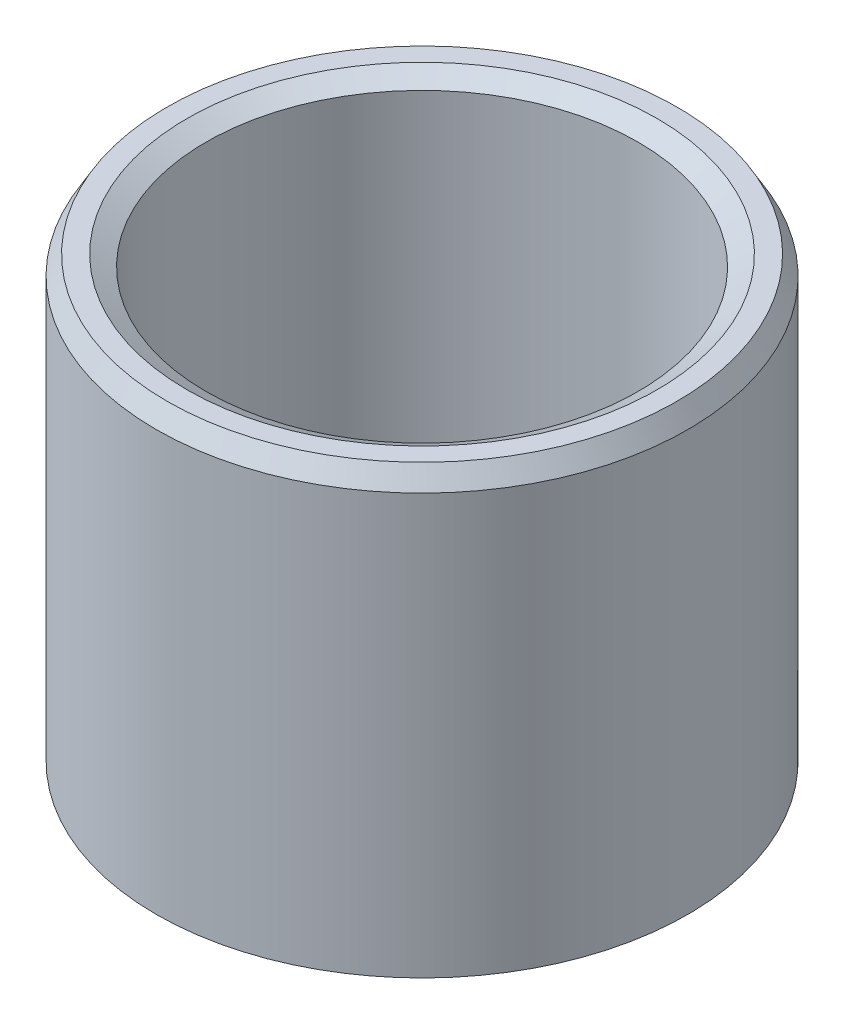
SolidWorks part; units mm, degrees
ref_plane "Front Plane" through (0, 0, 0) normal (0, 0, 1) x (1, 0, 0)
ref_plane "Top Plane" through (0, 0, 0) normal (0, 1, 0) x (1, 0, 0)
ref_plane "Right Plane" through (0, 0, 0) normal (1, 0, 0) x (0, 0, -1)
sketch "Sketch1" plane through (0, 0, 0) normal (0, 1, 0) x (1, 0, 0)
  circle A0 centre (0, 0) radius 15
  dimension "SLEEVE_OD" = 30
extrude "Boss-Extrude1" add sketch "Sketch1" along normal blind 25.377
sketch "Sketch2" plane through (0, 0, 0) normal (0, 1, 0) x (1, 0, 0)
  circle A0 centre (0, 0) radius 12.1884
  dimension "BORE_D" = 24.3769
extrude "Cut-Extrude1" cut sketch "Sketch2" along normal through all
chamfer "Chamfer1" distance 1.0704 angle 30 4 edges at (0, 25.377, 12.1884) (0, 0, 12.1884) (0, 0, 15) (0, 25.377, 15) first distance on face at (0, 25.377, 12.1884) first distance on face at (0, 0, 12.1884) first distance on face at (0, 25.377, 15)
